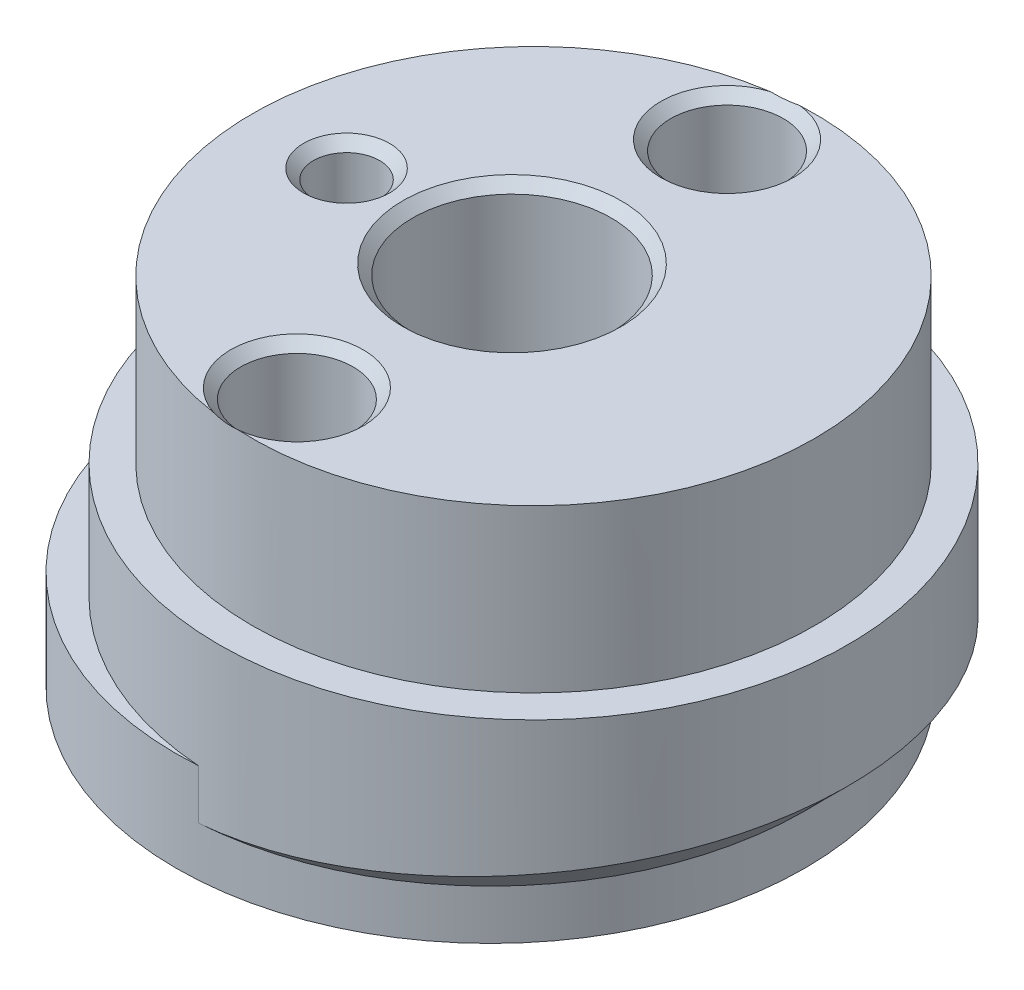
SolidWorks part; units mm, degrees
ref_plane "Front Plane" through (0, 0, 0) normal (0, 0, 1) x (1, 0, 0)
ref_plane "Top Plane" through (0, 0, 0) normal (0, 1, 0) x (1, 0, 0)
ref_plane "Right Plane" through (0, 0, 0) normal (1, 0, 0) x (0, 0, -1)
sketch "Sketch1" plane through (0, 0, 0) normal (0, 1, 0) x (1, 0, 0)
  circle A0 centre (0, 0) radius 3
  circle A2 centre (-0.65, 0) radius 9.5
  dimension "D1" = 6
  dimension "D2" = 19
  dimension "D3" = 0.65
extrude "Boss-Extrude1" add sketch "Sketch1" along normal blind 3
sketch "Sketch7" plane through (0, 3, 0) normal (0, 1, 0) x (1, 0, 0)
  circle A0 centre (0.65, 0) radius 8.5
  circle A1 centre (0, 0) radius 3 construction
  circle A2 centre (0, 0) radius 3
  dimension "D1" = 17
  dimension "D2" = 0.65
extrude "Boss-Extrude5" add sketch "Sketch7" along normal blind 8.4
sketch "Sketch8" plane through (0, 3, 0) normal (0, 1, 0) x (1, 0, 0)
  circle A0 centre (0.65, 0) radius 8.5 construction
  circle A1 centre (0.65, 0) radius 8.5
  circle A2 centre (0.65, 0) radius 9.5
  dimension "D1" = 19
extrude "Boss-Extrude6" add sketch "Sketch8" along normal blind 3.5
chamfer "Chamfer1" distance 1.5 angle 45 1 edges at (8.85, 3, 0)
sketch "Sketch12" plane through (0, 11.4, 0) normal (0, 1, 0) x (1, 0, 0)
  circle A0 centre (0.65, 0) radius 8.5 construction
  circle A1 centre (0, 0) radius 3 construction
  circle A2 centre (0.65, 0) radius 8.5 construction
  circle A3 centre (0, 0) radius 3
  circle A4 centre (-5, 0) radius 1
  dimension "D1" = 2
  dimension "D2" = 5
extrude "Cut-Extrude4" cut sketch "Sketch12" against normal through all
hole_wizard "M3 Clearance Hole1" positions "Sketch11" profile "Sketch10" hole size "M3" standard "DIN" end condition through all
sketch "Sketch11" plane through (0, 11.4, 0) normal (0, 1, 0) x (1, 0, 0)
  circle A0 centre (0, 0) radius 3 construction
  circle A1 centre (0, 0) radius 3
  circle A2 centre (0, 0) radius 6.5
  point P58 (0, 6.5)
  point P60 (0, -6.5)
  dimension "D1" = 13
sketch "Sketch10" plane through (0, 11.4, -6.5) normal (1, 0, 0) x (0, 0, 1)
  line L0 (0, 0) -> (0, 11.4)
  line L1 (0, 11.4) -> (1.7, 11.4)
  line L2 (1.7, 11.4) -> (1.7, 0)
  line L5 (1.7, 0) -> (0, 0)
  line L11 (0, -6.35) -> (0, 107.95) construction
  dimension "Thru Hole Dia." = 3.4
  dimension "Thru Hole Depth" = 11.4
chamfer "Chamfer2" distance 0.3 angle 45 8 edges at (0, 11.4, 8.2) (0, 11.4, -4.8) (0, 11.4, 3) (-5, 11.4, 1) (0, 0, -4.8) (-5, 0, 1) (0, 0, 8.2) (0, 0, 3)
